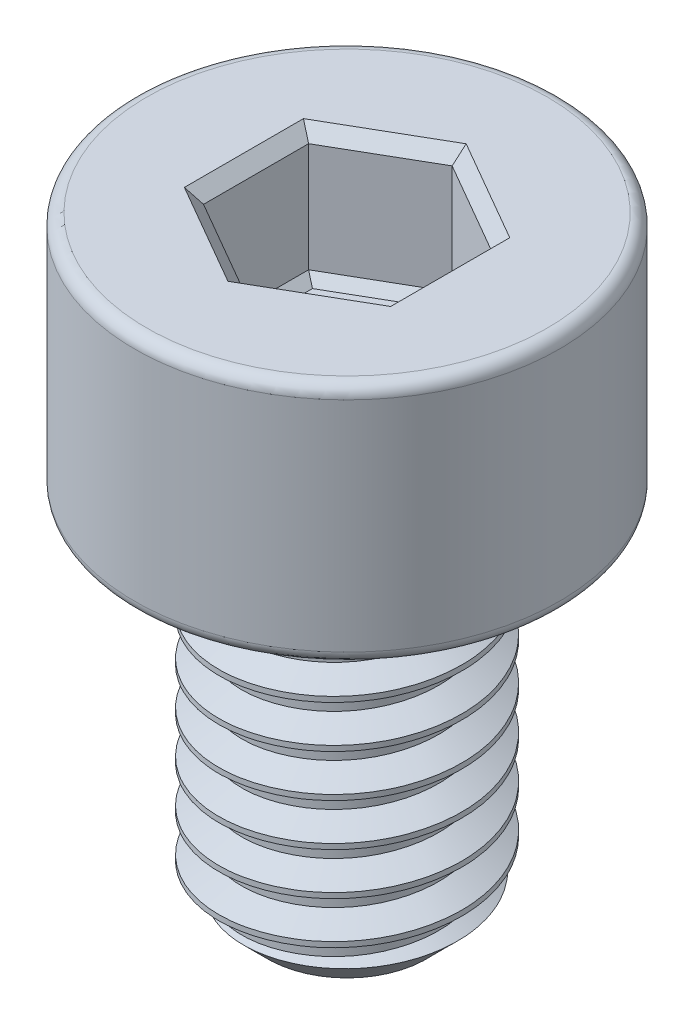
SolidWorks part; units mm, degrees
material "AISI Type A2 Tool Steel"
ref_plane "Front Plane" through (0, 0, 0) normal (0, 0, 1) x (1, 0, 0)
ref_plane "Top Plane" through (0, 0, 0) normal (0, 1, 0) x (1, 0, 0)
ref_plane "Right Plane" through (0, 0, 0) normal (1, 0, 0) x (0, 0, -1)
sketch "Sketch1" plane through (0, 0, 0) normal (0, 1, 0) x (1, 0, 0)
  circle A0 centre (0, 0) radius 2
  dimension "D1" = 4
extrude "Boss-Extrude1" add sketch "Sketch1" along normal blind 6
thread "Thread1" pitch 0.7 method cut profile "Thread Profile1" start angle 0, offset 1, length 0, pitch 0.7, diameter 4
ref_plane "Plane1" through (2, -1, 0) normal (0, 0, 1) x (1, 0, 0)
sketch "Thread Profile1" plane through (2, -1, 0) normal (0, 0, 1) x (1, 0, 0)
  line L0 (0, 0) -> (0, 0.7) construction
  line L11 (0, 0) -> (0, 0.6125)
  line L12 (0, 0.6125) -> (-0.3789, 0.3937)
  line L13 (-0.3789, 0.3937) -> (-0.3789, 0.2187)
  line L15 (-0.3789, 0.2187) -> (0, 0)
  line L17 (-0.3789, 0.3062) -> (0, 0.3062) construction
  point P2 (0, 0)
  dimension "Pitch" = 0.7
  dimension "Profile_Angle" = 60
  dimension "Profile_Land" = 0.175
  dimension "Profile_Height" = 0.3789
sketch "Sketch4" plane through (0, 6, 0) normal (0, -1, 0) x (-1, 0, 0)
  circle A0 centre (0, 0) radius 3.5
  dimension "D1" = 7
extrude "Boss-Extrude2" add sketch "Sketch4" against normal blind 4
fillet "Fillet1" radius 0.2 2 edges at (0, 6, -3.5) (0, 10, -3.5)
sketch "Sketch6" plane through (0, 0, 0) normal (0, 0, 1) x (1, 0, 0)
  line L0 (0, 0) -> (2.01, 0) construction
  line L1 (2.01, 0) -> (2.01, 0.7)
  line L2 (2.01, 0.7) -> (1.31, 0)
  line L3 (1.31, 0) -> (2.01, 0)
  line L4 (0, 0) -> (0, 0.3482) construction
  dimension "D1" = 0.7
  dimension "D2" = 45
  dimension "D3" = 2.01
revolve "Cut-Revolve1" cut sketch "Sketch6" angle 360 about L4
sketch "Sketch7" plane through (0, 10, 0) normal (0, 1, 0) x (1, 0, 0)
  line L1 (0, 1.7321) -> (-1.5, 0.866)
  line L2 (-1.5, 0.866) -> (-1.5, -0.866)
  line L3 (-1.5, -0.866) -> (0, -1.7321)
  line L4 (0, -1.7321) -> (1.5, -0.866)
  line L5 (1.5, -0.866) -> (1.5, 0.866)
  line L6 (1.5, 0.866) -> (0, 1.7321)
  circle A0 centre (0, 0) radius 1.5 construction
  dimension "D1" = 3
extrude "Cut-Extrude1" cut sketch "Sketch7" against normal blind 2
chamfer "Chamfer1" distance 0.2 angle 45 6 edges at (-1.5, 10, 0) (-0.75, 10, 1.299) (0.75, 10, 1.299) (1.5, 10, 0) (0.75, 10, -1.299) (-0.75, 10, -1.299)
sketch "Sketch8" plane through (0, 8, 0) normal (0, 1, 0) x (1, 0, 0)
  line L1 (0, 1.7321) -> (-1.5, 0.866)
  line L2 (-1.5, 0.866) -> (-1.5, -0.866)
  line L3 (-1.5, -0.866) -> (0, -1.7321)
  line L4 (0, -1.7321) -> (1.5, -0.866)
  line L5 (1.5, -0.866) -> (1.5, 0.866)
  line L6 (1.5, 0.866) -> (0, 1.7321)
  circle A0 centre (0, 0) radius 1.5 construction
extrude "Cut-Extrude2" cut sketch "Sketch8" against normal blind 0.15 draft 45
